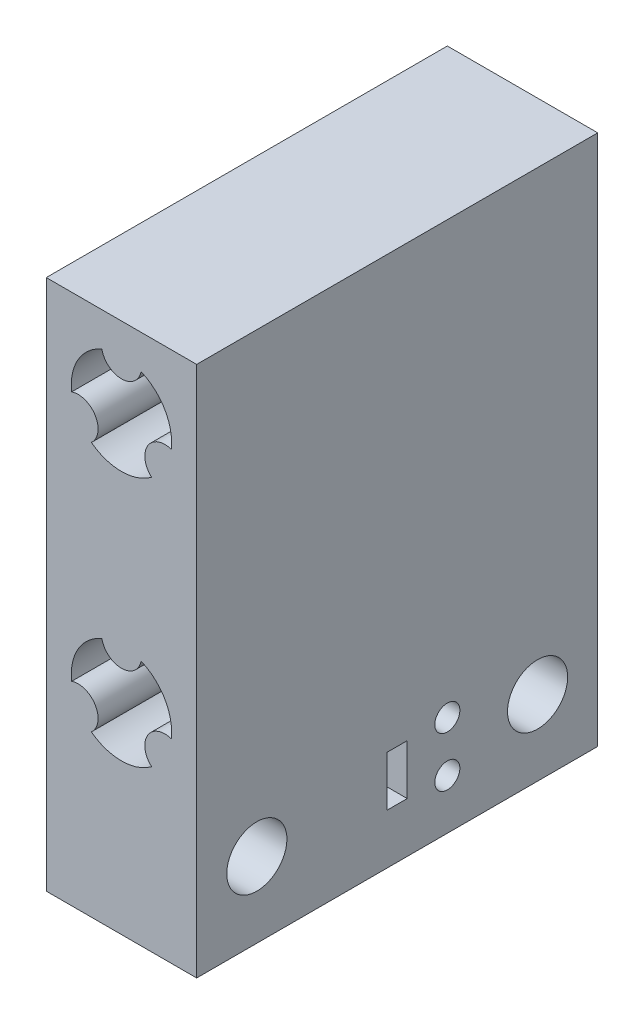
SolidWorks part; units mm, degrees
ref_plane "Front Plane" through (0, 0, 0) normal (0, 0, 1) x (1, 0, 0)
ref_plane "Top Plane" through (0, 0, 0) normal (0, 1, 0) x (1, 0, 0)
ref_plane "Right Plane" through (0, 0, 0) normal (1, 0, 0) x (0, 0, -1)
sketch "Sketch1" plane through (0, 0, 0) normal (0, 0, 1) x (1, 0, 0)
  line L0 (0, 15.875) -> (0, -15.875) construction
  line L1 (9.525, 28.575) -> (-9.525, 28.575)
  line L2 (9.525, 28.575) -> (9.525, -28.575)
  line L3 (9.525, -28.575) -> (-9.525, -28.575)
  line L4 (-9.525, 28.575) -> (-9.525, -28.575)
  line L5 (9.525, 28.575) -> (-9.525, -28.575) construction
  line L6 (9.525, -28.575) -> (-9.525, 28.575) construction
  circle A0 centre (0, 15.875) radius 3.81
  circle A1 centre (0, -15.875) radius 3.81
  circle A2 centre (0, -15.875) radius 6.35
  circle A3 centre (0, 15.875) radius 6.35
  circle A4 centre (0, -9.525) radius 2.54
  circle A5 centre (5.4993, -19.05) radius 2.54
  circle A6 centre (-5.4993, -19.05) radius 2.54
  circle A7 centre (0, 22.225) radius 2.54
  circle A8 centre (5.4993, 12.7) radius 2.54
  circle A9 centre (-5.4993, 12.7) radius 2.54
  point P0 (0, 0)
  point P9 (0, 0)
  point P15 (3.2996, -17.78)
  point P17 (3.815, -20.9513)
  point P22 (6.3037, -16.6407)
  dimension "D4" = 7.62
  dimension "D5" = 7.62
  dimension "D6" = 12.7
  dimension "D7" = 12.7
  dimension "D9" = 3
  dimension "D1" = 57.15
  dimension "D2" = 19.05
  dimension "D3" = 31.75
  dimension "D8" = 3
extrude "Boss-Extrude1" add sketch "Sketch1" along normal blind 50.8 contours L2 L1 L4 L3
extrude "Cut-Extrude1" cut sketch "Sketch1<4>" along normal through all contours A2
sketch "Sketch1<4>" plane through (0, 0, 0) normal (0, 0, 1) x (1, 0, 0) same geometry as "Sketch1"
extrude "Boss-Extrude2" add sketch "Sketch1<5>" along normal through all contours A4 | A6 | A5
sketch "Sketch1<5>" plane through (0, 0, 0) normal (0, 0, 1) x (1, 0, 0) same geometry as "Sketch1"
extrude "Cut-Extrude2" cut sketch "Sketch1<6>" along normal through all contours A3
sketch "Sketch1<6>" plane through (0, 0, 0) normal (0, 0, 1) x (1, 0, 0) same geometry as "Sketch1"
extrude "Boss-Extrude3" add sketch "Sketch1<7>" along normal through all contours A9 | A7 | A8
sketch "Sketch1<7>" plane through (0, 0, 0) normal (0, 0, 1) x (1, 0, 0) same geometry as "Sketch1"
sketch "Sketch11" plane through (0, 28.575, 0) normal (0, 1, 0) x (1, 0, 0)
  line L1 (-9.525, 0) -> (9.525, 0)
  line L2 (-9.525, 0) -> (-9.525, -50.8)
  line L3 (-9.525, -50.8) -> (9.525, -50.8)
  line L4 (9.525, 0) -> (9.525, -50.8)
extrude "Cut-Extrude12" cut sketch "Sketch11" against normal blind 2.54
sketch "Sketch12" plane through (0, -28.575, 0) normal (0, -1, 0) x (1, 0, 0)
  line L1 (-9.525, 50.8) -> (9.525, 50.8)
  line L2 (-9.525, 50.8) -> (-9.525, 0)
  line L3 (-9.525, 0) -> (9.525, 0)
  line L4 (9.525, 50.8) -> (9.525, 0)
extrude "Boss-Extrude4" add sketch "Sketch12" along normal blind 12.7
sketch "Sketch13" plane through (9.525, 0, 0) normal (1, 0, 0) x (0, 0, -1)
  line L0 (-50.8, -41.275) -> (-50.8, -31.75) construction
  line L1 (-50.8, 26.035) -> (-50.8, -41.275) construction
  line L2 (-50.8, -31.75) -> (0, -31.75) construction
  line L3 (0, 26.035) -> (0, -41.275) construction
  line L4 (0, -31.75) -> (-7.62, -31.75)
  line L5 (-50.8, -41.275) -> (-50.8, -31.75)
  line L6 (0, -31.75) -> (0, -41.275)
  line L7 (0, -33.5271) -> (0, -36.3229)
  line L8 (-50.8, -33.5271) -> (-50.8, -36.3229)
  line L10 (-24.13, -34.925) -> (-26.67, -34.925)
  line L11 (-24.13, -34.925) -> (-24.13, -28.575)
  line L12 (-24.13, -28.575) -> (-26.67, -28.575)
  line L13 (-26.67, -34.925) -> (-26.67, -28.575)
  line L14 (-24.13, -34.925) -> (-26.67, -28.575) construction
  line L15 (-24.13, -28.575) -> (-26.67, -34.925) construction
  line L16 (-24.13, -34.925) -> (-19.05, -34.925) construction
  line L17 (-24.13, -34.925) -> (-24.13, -28.575)
  line L18 (-24.13, -28.575) -> (-19.05, -28.575) construction
  line L19 (-19.05, -34.925) -> (-19.05, -28.575) construction
  circle A0 centre (-43.18, -31.75) radius 3.81
  circle A1 centre (-43.18, -31.75) radius 6.35
  circle A2 centre (-7.62, -31.75) radius 3.81
  circle A3 centre (-7.62, -31.75) radius 6.35
  circle A4 centre (-43.18, -25.4) radius 2.54
  circle A5 centre (-37.6807, -34.925) radius 2.54
  arc A6 (-50.8, -36.3229) -> (-50.8, -33.5271) centre (-48.6793, -34.925) ccw
  circle A7 centre (-7.62, -25.4) radius 2.54
  arc A8 (0, -33.5271) -> (0, -36.3229) centre (-2.1207, -34.925) ccw
  circle A9 centre (-13.1193, -34.925) radius 2.54
  circle A10 centre (-19.05, -28.575) radius 1.5875
  circle A11 centre (-19.05, -34.925) radius 1.5875
  point P25 (-25.4, -31.75)
  dimension "D2" = 7.62
  dimension "D4" = 12.7
  dimension "D6" = 7.62
  dimension "D7" = 12.7
  dimension "D13" = 3.175
  dimension "D14" = 3.175
  dimension "D1" = 9.525
  dimension "D3" = 7.62
  dimension "D5" = 7.62
  dimension "D10" = 6.35
  dimension "D11" = 2.54
  dimension "D12" = 5.08
  dimension "D8" = 3
  dimension "D9" = 3
extrude "Cut-Extrude15" cut sketch "Sketch13" against normal through all contours A2 | A0
extrude "Cut-Extrude16" cut sketch "Sketch13<6>" against normal through all contours L12 L13 L10 L11
sketch "Sketch13<6>" plane through (9.525, 0, 0) normal (1, 0, 0) x (0, 0, -1) same geometry as "Sketch13"
extrude "Cut-Extrude17" cut sketch "Sketch13<7>" against normal through all contours A11 | A10
sketch "Sketch13<7>" plane through (9.525, 0, 0) normal (1, 0, 0) x (0, 0, -1) same geometry as "Sketch13"
